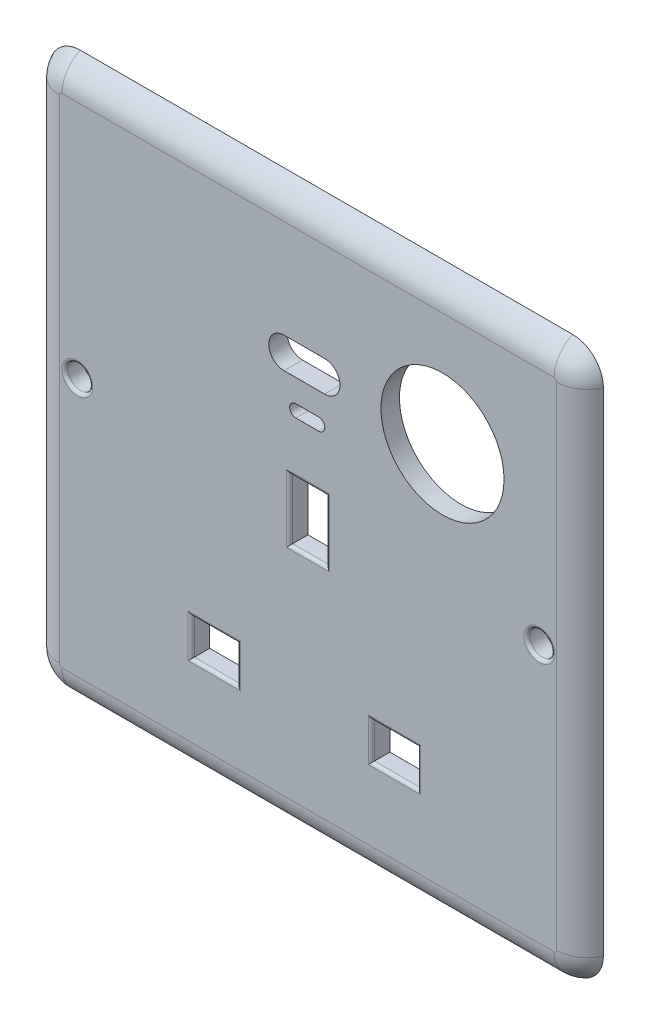
SolidWorks part; units mm, degrees
ref_plane "Front Plane" through (0, 0, 0) normal (0, 0, 1) x (1, 0, 0)
ref_plane "Top Plane" through (0, 0, 0) normal (0, 1, 0) x (1, 0, 0)
ref_plane "Right Plane" through (0, 0, 0) normal (1, 0, 0) x (0, 0, -1)
sketch "Sketch1" plane through (0, 0, 0) normal (0, 0, 1) x (1, 0, 0)
  line L1 (10.6968, 36) -> (100.6968, 36)
  line L2 (10.6968, 36) -> (10.6968, -54)
  line L3 (10.6968, -54) -> (100.6968, -54)
  line L4 (100.6968, 36) -> (100.6968, -54)
  dimension "D1" = 90
  dimension "D2" = 90
extrude "Boss-Extrude5" add sketch "Sketch1" along normal blind 3 contours L1 L4 L3 L2
fillet "Fillet14" radius 5 4 edges at (10.6968, 36, 1.5) (10.6968, -54, 1.5) (100.6968, -54, 1.5) (100.6968, 36, 1.5)
fillet "Fillet15" radius 5 8 edges at (12.1612, 34.5355, 3) (55.6968, 36, 3) (99.2323, 34.5355, 3) (100.6968, -9, 3) (99.2323, -52.5355, 3) (55.6968, -54, 3) (12.1612, -52.5355, 3) (10.6968, -9, 3)
sketch "Sketch17" plane through (0, 0, 3) normal (0, 0, 1) x (1, 0, 0)
  line L0 (65.9895, -31.6532) -> (73.4895, -31.6532)
  line L1 (52.6878, -3.7163) -> (58.6878, -3.7163)
  line L2 (52.6878, -3.7163) -> (52.6878, -13.7163)
  line L3 (52.6878, -13.7163) -> (58.6878, -13.7163)
  line L4 (58.6878, -3.7163) -> (58.6878, -13.7163)
  line L5 (36.7153, -31.675) -> (44.2153, -31.675)
  line L6 (36.7153, -31.675) -> (36.7153, -37.675)
  line L7 (36.7153, -37.675) -> (44.2153, -37.675)
  line L8 (44.2153, -31.675) -> (44.2153, -37.675)
  line L9 (65.9895, -31.6532) -> (65.9895, -37.6532)
  line L10 (65.9895, -37.6532) -> (73.4895, -37.6532)
  line L11 (73.4895, -31.6532) -> (73.4895, -37.6532)
  line L12 (53.7073, 5.7459) -> (57.4234, 5.7459) construction
  line L13 (53.7073, 6.7459) -> (57.4234, 6.7459)
  line L14 (53.7073, 4.7459) -> (57.4234, 4.7459)
  line L15 (51.8071, 12.9453) -> (58.394, 12.9453) construction
  line L16 (51.8071, 15.4453) -> (58.394, 15.4453)
  line L17 (51.8071, 10.4453) -> (58.394, 10.4453)
  arc A0 (53.7073, 6.7459) -> (53.7073, 4.7459) centre (53.7073, 5.7459) ccw
  arc A1 (57.4234, 4.7459) -> (57.4234, 6.7459) centre (57.4234, 5.7459) ccw
  circle A2 centre (77.5517, 13.0099) radius 10
  arc A4 (51.8071, 15.4453) -> (51.8071, 10.4453) centre (51.8071, 12.9453) ccw
  arc A5 (58.394, 10.4453) -> (58.394, 15.4453) centre (58.394, 12.9453) ccw
  circle A6 centre (18.1994, -7.4072) radius 2
  circle A7 centre (93.2637, -7.4072) radius 2
  point P14 (55.5653, 5.7459)
  point P25 (55.1006, 12.9453)
extrude "Cut-Extrude4" cut sketch "Sketch17" against normal blind 3
fillet "Fillet16" radius 0.5 14 edges at (20.1994, -7.4072, 3) (95.2637, -7.4072, 3) (58.6878, -8.7163, 3) (55.6878, -13.7163, 3) (52.6878, -8.7163, 3) (55.6878, -3.7163, 3) (69.7395, -31.6532, 3) (73.4895, -34.6532, 3) (65.9895, -34.6532, 3) (69.7395, -37.6532, 3) (40.4653, -37.675, 3) (44.2153, -34.675, 3) (36.7153, -34.675, 3) (40.4653, -31.675, 3)
